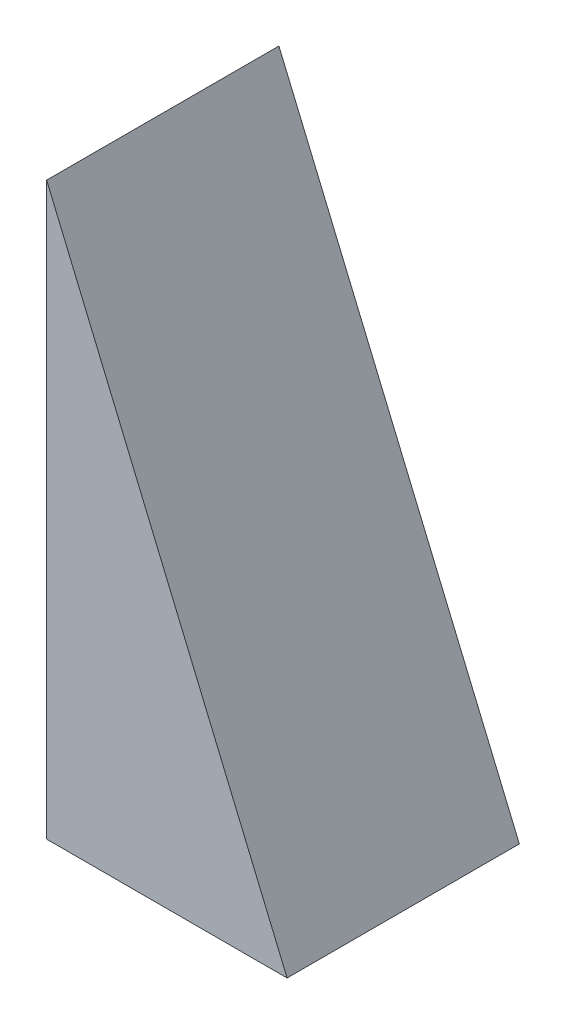
SolidWorks part; units mm, degrees
ref_plane "Front Plane" through (0, 0, 0) normal (0, 0, 1) x (1, 0, 0)
ref_plane "Top Plane" through (0, 0, 0) normal (0, 1, 0) x (1, 0, 0)
ref_plane "Right Plane" through (0, 0, 0) normal (1, 0, 0) x (0, 0, -1)
sketch "Sketch1" plane through (0, 0, 0) normal (0, 0, 1) x (1, 0, 0)
  line L0 (0, 0) -> (0, 23.408)
  line L1 (0, 23.408) -> (9.8604, 0)
  line L2 (9.8604, 0) -> (0, 0)
  dimension "D1" = 25.4
extrude "Boss-Extrude1" add sketch "Sketch1" along normal blind 9.525
